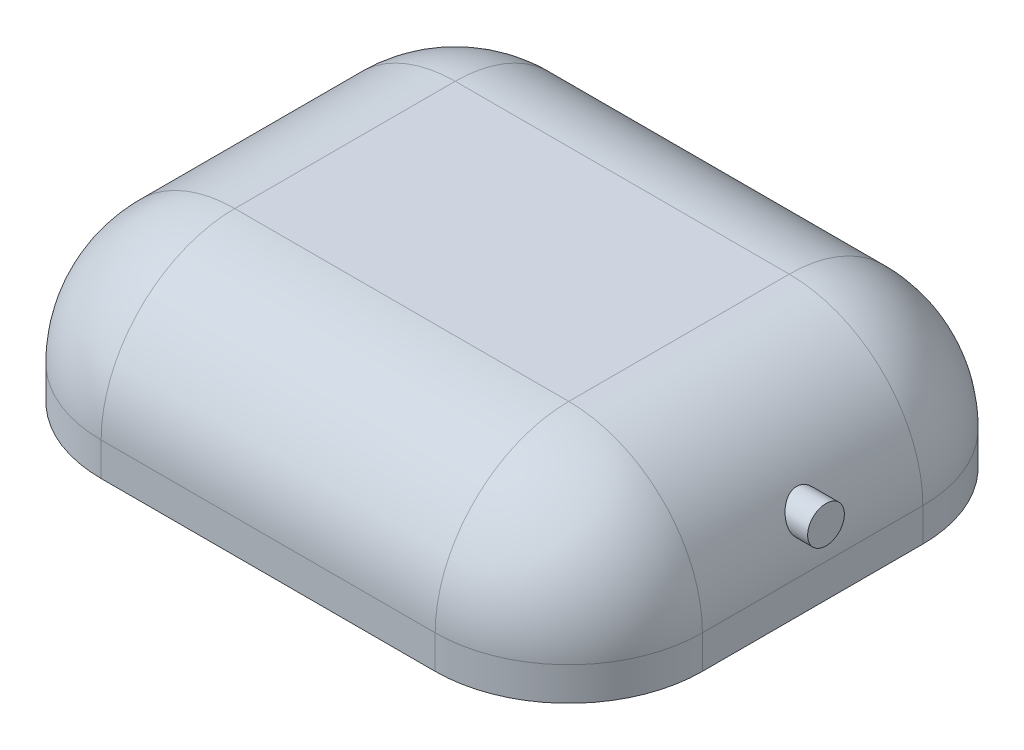
SolidWorks part; units mm, degrees
ref_plane "Front Plane" through (0, 0, 0) normal (0, 0, 1) x (1, 0, 0)
ref_plane "Top Plane" through (0, 0, 0) normal (0, 1, 0) x (1, 0, 0)
ref_plane "Right Plane" through (0, 0, 0) normal (1, 0, 0) x (0, 0, -1)
sketch "Sketch1" plane through (0, 0, 0) normal (0, 1, 0) x (1, 0, 0)
  line L1 (-22.5, -18.25) -> (22.5, -18.25)
  line L2 (-22.5, -18.25) -> (-22.5, 18.25)
  line L3 (-22.5, 18.25) -> (22.5, 18.25)
  line L4 (22.5, -18.25) -> (22.5, 18.25)
  line L5 (-22.5, -18.25) -> (22.5, 18.25) construction
  line L6 (-22.5, 18.25) -> (22.5, -18.25) construction
  point P0 (0, 0)
  dimension "D1" = 45
  dimension "D2" = 36.5
extrude "Boss-Extrude1" add sketch "Sketch1" along normal blind 12.5 contours L3 L4 L1 L2
sketch "Sketch2" plane through (22.5, 0, 0) normal (1, 0, 0) x (0, 0, -1)
  circle A0 centre (0, 5.8846) radius 1.375
  dimension "D1" = 2.75
extrude "Boss-Extrude2" add sketch "Sketch2" along normal blind 1
hole_wizard "Tap Drill for M2.5x0.45 Tap1" positions "Sketch4" profile "Sketch3" hole size "M2.5x0.45" standard "ANSI Metric"
sketch "Sketch4" plane through (0, 0, 0) normal (0, -1, 0) x (-1, 0, 0)
  line L1 (22.5, -18.25) -> (-22.5, -18.25) construction
  line L2 (22.5, -18.25) -> (22.5, 18.25) construction
  line L3 (22.5, 18.25) -> (-22.5, 18.25) construction
  point P0 (15.6, 7.25)
  point P1 (-14.1, -7.65)
  dimension "D1" = 36.6
  dimension "D2" = 10.6
  dimension "D3" = 11
  dimension "D4" = 6.9
sketch "Sketch3" plane through (-15.6, 0, -7.25) normal (1, 0, 0) x (0, 0, -1)
  line L0 (0, 0) -> (0, 3.6159)
  line L1 (0, 3.6159) -> (1.025, 3)
  line L2 (1.025, 3) -> (1.025, 0)
  line L5 (1.025, 0) -> (0, 0)
  line L10 (0, 3.6159) -> (-1.025, 3) construction
  line L11 (0, -6.35) -> (0, 107.95) construction
  dimension "Hole Dia." = 2.05
  dimension "Hole Depth" = 3
  dimension "Drill Angle" = 118
fillet "Fillet1" radius 10 8 edges at (22.5, 6.25, -18.25) (22.5, 6.25, 18.25) (-22.5, 6.25, -18.25) (-22.5, 6.25, 18.25) (22.5, 12.5, 0) (0, 12.5, -18.25) (-22.5, 12.5, 0) (0, 12.5, 18.25)
